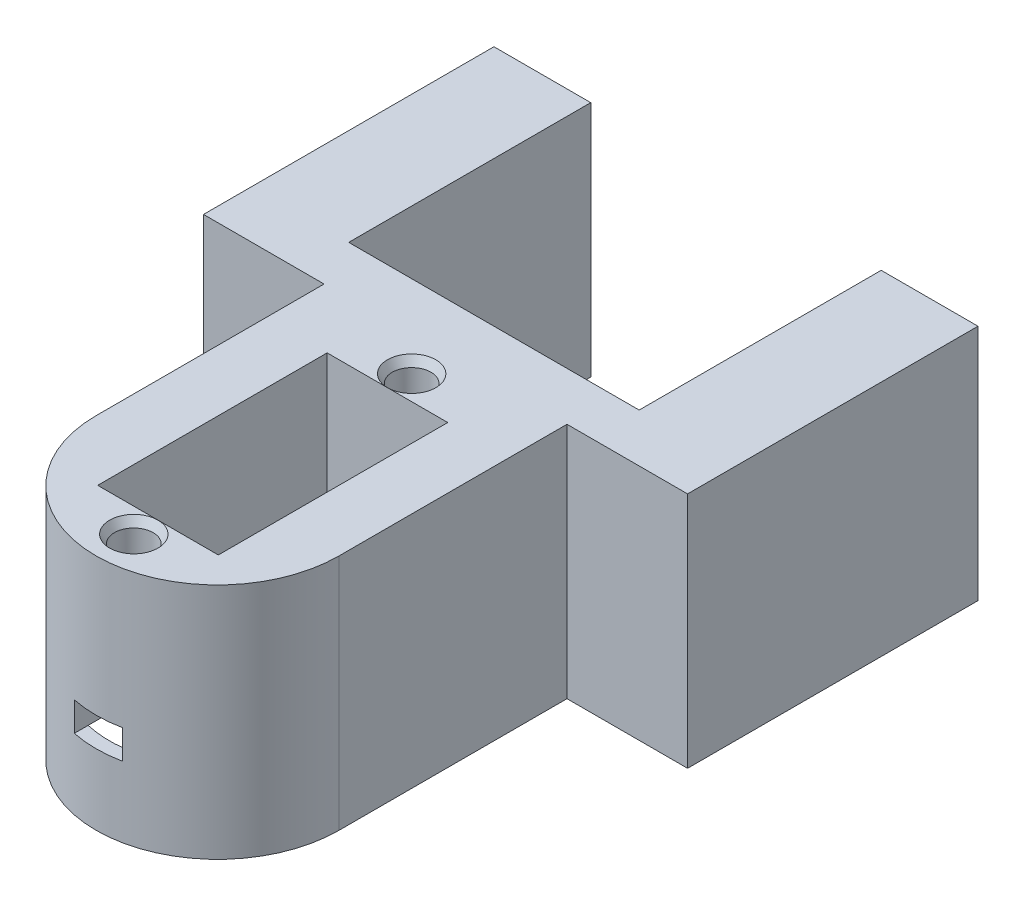
SolidWorks part; units mm, degrees
ref_plane "Front Plane" through (0, 0, 0) normal (0, 0, 1) x (1, 0, 0)
ref_plane "Top Plane" through (0, 0, 0) normal (0, 1, 0) x (1, 0, 0)
ref_plane "Right Plane" through (0, 0, 0) normal (1, 0, 0) x (0, 0, -1)
sketch "Sketch4" plane through (0, 0, 0) normal (0, 0, 1) x (1, 0, 0)
  line L1 (-6.23, 55.25) -> (6.23, 55.25)
  line L2 (-6.23, 55.25) -> (-6.23, 72.5)
  line L3 (-6.23, 72.5) -> (6.23, 72.5)
  line L4 (6.23, 55.25) -> (6.23, 72.5)
  point P4 (0, 72.5)
  dimension "D1" = 12.46
  dimension "D2" = 17.25
extrude "Boss-Extrude3" add sketch "Sketch4" along normal blind 6
sketch "Sketch8" plane through (0, 55.25, 0) normal (0, -1, 0) x (-1, 0, 0)
  circle A0 centre (0, -23.55) radius 12.5468
  circle A1 centre (0, -23.55) radius 11.15
  point P3 (0, 0)
  dimension "D1" = 22.3
  dimension "D2" = 23.55
extrude "Boss-Extrude6" add sketch "Sketch8" along normal blind 7.3 and the other way up to surface (17.25 mm away) other way up to face at (0, 72.5, 3)
sketch "Sketch5" plane through (0, 72.5, 0) normal (0, 1, 0) x (1, 0, 0)
  line L8 (12.5468, -23.55) -> (12.5468, 0)
  line L9 (12.5468, 0) -> (6.23, 0)
  line L10 (-12.5468, -23.55) -> (-12.5468, 0)
  line L11 (-12.5468, 0) -> (-6.23, 0)
  line L12 (-6.23, 0) -> (-6.23, -29.7)
  line L14 (6.23, -29.7) -> (6.23, 0)
  line L15 (-6.23, -29.7) -> (6.23, -29.7)
  line L16 (6.23, -6) -> (-6.23, -6) construction
  circle A0 centre (0, -23.55) radius 12.5468 construction
  arc A1 (-12.5468, -23.55) -> (12.5468, -23.55) centre (0, -23.55) ccw
  point P9 (-6.9251, -2.8951)
  point P10 (0, 0)
  point P11 (6.9251, -1.2536)
  point P19 (0, 0)
  point P20 (0, 0)
  dimension "D1" = 23.7
  dimension "D2" = 23.55
extrude "Boss-Extrude4" add sketch "Sketch5" against normal up to surface (17.25 mm away) up to face at (0, 55.25, 3)
sketch "Sketch6" plane through (0, 72.5, 0) normal (0, 1, 0) x (1, 0, 0)
  line L0 (6.23, -6) -> (-6.23, -6) construction
  line L3 (6.23, -29.7) -> (-6.23, -29.7) construction
  circle A0 centre (0, -3.5) radius 2
  circle A1 centre (0, -32.2) radius 2
  point P2 (0, 0)
  dimension "D1" = 4
  dimension "D3" = 4
  dimension "D2" = 2.5
  dimension "D4" = 2.5
extrude "Cut-Extrude1" cut sketch "Sketch6" against normal blind 5
chamfer "Chamfer1" distance 0.5 angle 60 2 edges at (0, 72.5, 5.5) (0, 72.5, 34.2) first distance on face at (0, 72.5, 5.5)
sketch "Sketch10" plane through (0, 72.5, 0) normal (0, 1, 0) x (1, 0, 0)
  line L1 (-6.23, -6) -> (6.23, -6)
  line L2 (-6.23, -6) -> (-6.23, -29.7)
  line L3 (-6.23, -29.7) -> (6.23, -29.7)
  line L4 (6.23, -6) -> (6.23, -29.7)
extrude "Cut-Extrude3" cut sketch "Sketch10" against normal up to surface (17.25 mm away) up to face at (0, 55.25, 10.3399)
ref_plane "Plane1" through (0, 0, 36.0968) normal (0, 0, 1) x (1, 0, 0)
sketch "Sketch11" plane through (0, 0, 36.0968) normal (0, 0, 1) x (1, 0, 0)
  line L0 (-11.15, 55.25) -> (11.15, 55.25) construction
  line L1 (-2.5, 58.25) -> (2.5, 58.25)
  line L2 (-2.5, 58.25) -> (-2.5, 55.25)
  line L3 (-2.5, 55.25) -> (2.5, 55.25)
  line L4 (2.5, 58.25) -> (2.5, 55.25)
  point P4 (0, 58.25)
  dimension "D1" = 0
  dimension "D2" = 5
  dimension "D3" = 3
extrude "Cut-Extrude4" cut sketch "Sketch11" against normal up to next
sketch "Sketch13" plane through (0, 47.95, 0) normal (0, -1, 0) x (1, 0, 0)
  line L0 (-12.5468, 23.55) -> (-12.5468, 0)
  line L1 (-12.5468, 0) -> (12.5468, 0)
  line L2 (12.5468, 0) -> (12.5468, 23.55)
  arc A0 (-12.5468, 23.55) -> (12.5468, 23.55) centre (0, 23.55) ccw
  point P3 (0, 0)
extrude "Boss-Extrude7" add sketch "Sketch13" against normal up to surface (7.3 mm away) up to face at (0, 55.25, 10.3399)
sketch "Sketch14" plane through (0, 72.5, 0) normal (0, 1, 0) x (1, 0, 0)
  line L0 (-25, 0) -> (-25, 30)
  line L1 (-25, 0) -> (25, 0)
  line L5 (-25, 30) -> (-15, 30)
  line L6 (-15, 30) -> (-15, 5)
  line L7 (-15, 5) -> (15, 5)
  line L8 (15, 5) -> (15, 30)
  line L9 (15, 30) -> (25, 30)
  line L10 (25, 30) -> (25, 0)
  point P1 (0, 0)
  point P5 (0, 0)
  point P11 (-3.1222, 5)
  point P12 (0, 5)
  point P14 (0, 0)
  dimension "D1" = 50
  dimension "D2" = 5
  dimension "D3" = 30
  dimension "D4" = 30
extrude "Boss-Extrude8" add sketch "Sketch14" against normal up to surface (24.55 mm away) up to face at (0, 47.95, 14.9117)
